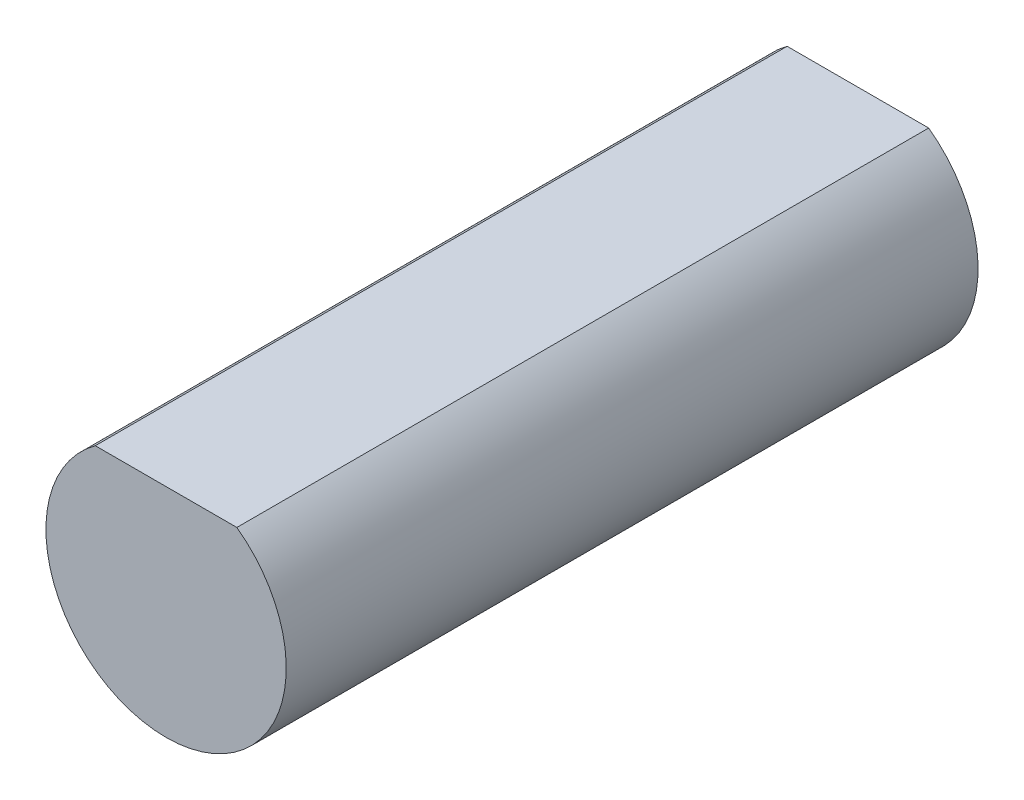
SolidWorks part; units mm, degrees
ref_plane "前视基准面" through (0, 0, 0) normal (0, 0, 1) x (1, 0, 0)
ref_plane "上视基准面" through (0, 0, 0) normal (0, 1, 0) x (1, 0, 0)
ref_plane "右视基准面" through (0, 0, 0) normal (1, 0, 0) x (0, 0, -1)
other "Configuration Table"
sketch "草图1" plane through (0, 0, 0) normal (0, 0, 1) x (1, 0, 0)
  circle A0 centre (0, 0) radius 9.9
  dimension "D1" = 19.8
extrude "凸台-拉伸1" add sketch "草图1" along normal blind 57
sketch "草图2" plane through (0, 0, 57) normal (0, 0, 1) x (1, 0, 0)
  line L0 (-6, 8) -> (6, 8)
  arc A0 (6, 8) -> (-6, 8) centre (0, 0) ccw
  dimension "D1" = 20
  dimension "D2" = 8
extrude "切除-拉伸1" cut sketch "草图2" against normal through all
